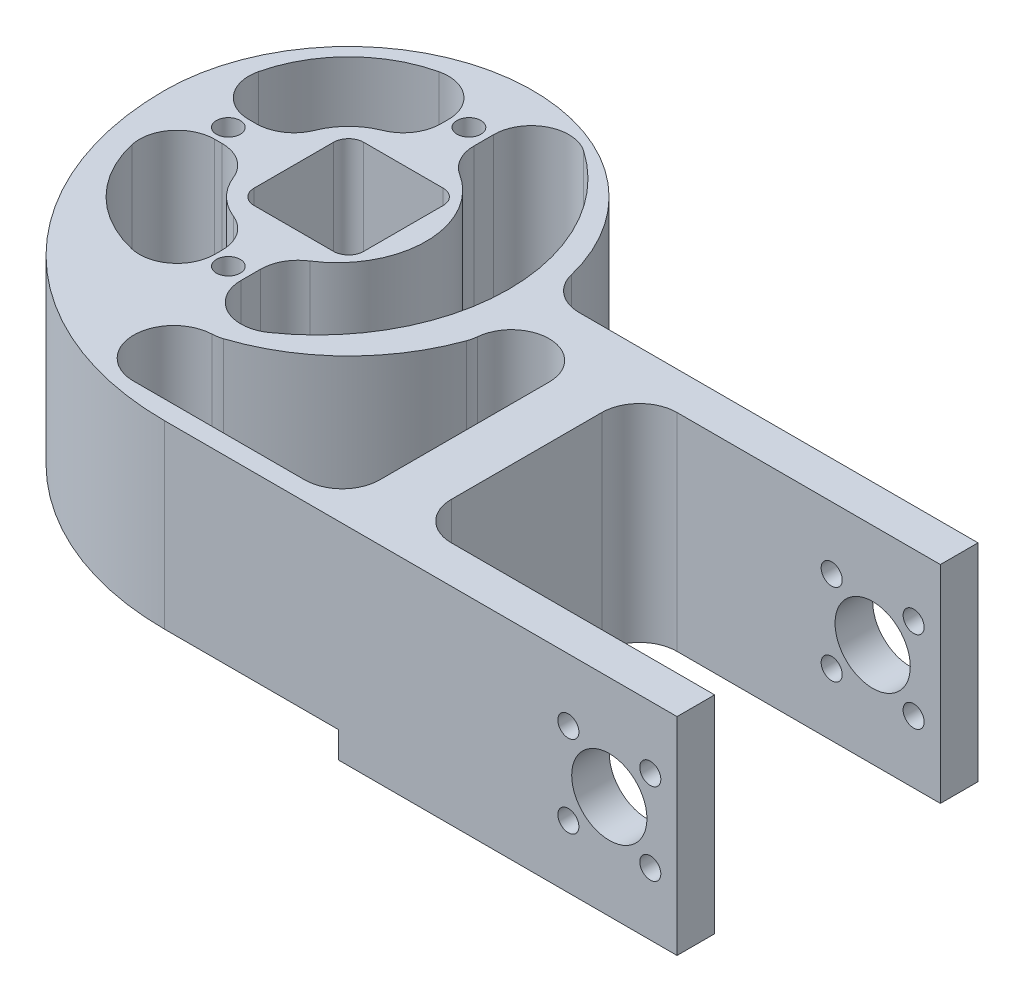
SolidWorks part; units mm, degrees
material "6061-T6 (SS)"
ref_plane "Front Plane" through (0, 0, 0) normal (0, 0, 1) x (1, 0, 0)
ref_plane "Top Plane" through (0, 0, 0) normal (0, 1, 0) x (1, 0, 0)
ref_plane "Right Plane" through (0, 0, 0) normal (1, 0, 0) x (0, 0, -1)
sketch "Sketch1" plane through (0, 0, 0) normal (0, 1, 0) x (1, 0, 0)
  circle A0 centre (0, 0) radius 31.0896
  dimension "D1" = 62.1792
extrude "Boss-Extrude1" add sketch "Sketch1" along normal blind 34.925
sketch "Sketch2" plane through (0, 34.925, 0) normal (0, 1, 0) x (1, 0, 0)
  line L0 (0, 0) -> (-31.0896, 0) construction
  line L1 (0, 0) -> (30.9857, 2.54) construction
  line L2 (46.5427, -48.26) -> (17.1704, -48.26)
  line L4 (46.5427, -48.26) -> (46.5427, 2.54)
  line L7 (30.9857, 2.54) -> (46.5427, 2.54)
  circle A0 centre (0, 0) radius 31.0896 construction
  arc A1 (17.1704, -48.26) -> (-31.0896, 0) centre (17.1704, 0) cw
  circle A2 centre (0, 0) radius 31.0896
  arc A3 (-31.0896, 0) -> (30.9857, 2.54) centre (0, 0) ccw
  dimension "D3" = 2.54
  dimension "D1" = 50.8
  dimension "D2" = 15.557
  dimension "D4" = 0
extrude "Boss-Extrude2" add sketch "Sketch2" against normal blind 30.48
sketch "Sketch3" plane through (0, 34.925, 0) normal (0, 1, 0) x (1, 0, 0)
  line L0 (46.5427, -0.3336) -> (46.5427, -48.26)
  line L1 (17.1704, -48.26) -> (46.5427, -48.26) construction
  line L2 (46.5427, -48.26) -> (103.6927, -48.26)
  line L3 (103.6927, -48.26) -> (103.6927, -41.91)
  line L4 (103.6927, -41.91) -> (52.8927, -41.91)
  line L5 (52.8927, -41.91) -> (52.8927, -3.81)
  line L6 (52.8927, -3.81) -> (103.6927, -3.81)
  line L7 (103.6927, -3.81) -> (103.6927, 2.54)
  line L8 (103.6927, 2.54) -> (46.5427, 2.54)
  line L9 (46.5427, -0.3336) -> (46.5427, 2.54)
  line L10 (46.5427, -48.26) -> (46.5427, 2.54) construction
  dimension "D1" = 57.15
  dimension "D2" = 38.1
  dimension "D3" = 6.35
  dimension "D4" = 6.35
extrude "Boss-Extrude3" add sketch "Sketch3" against normal up to surface (34.925 mm away) up to face at (0, 0, 31.0896)
sketch "Sketch4" plane through (0, 0, -2.54) normal (0, 0, -1) x (-1, 0, 0)
  line L0 (-103.6927, 17.4625) -> (-92.2627, 17.4625) construction
  line L1 (-103.6927, 0) -> (-103.6927, 34.925) construction
  line L2 (-92.2627, 17.4625) -> (-99.1775, 10.5477) construction
  line L3 (-92.2627, 17.4625) -> (-99.1775, 24.3773) construction
  line L4 (-92.2627, 17.4625) -> (-99.1775, 10.5477) construction
  line L5 (-92.2627, 17.4625) -> (-85.3479, 10.5477) construction
  line L6 (-92.2627, 17.4625) -> (-85.3479, 24.3773) construction
  line L8 (-99.1775, 24.3773) -> (-103.6927, 24.3773) construction
  line L9 (-103.6927, 0) -> (-103.6927, 34.925) construction
  line L10 (-99.1775, 10.5477) -> (-103.6927, 10.5477) construction
  circle A0 centre (-92.2627, 17.4625) radius 6.35
  circle A1 centre (-85.3479, 10.5477) radius 1.778
  circle A3 centre (-99.1775, 24.3773) radius 1.778
  circle A4 centre (-99.1775, 10.5477) radius 1.778
  circle A5 centre (-85.3479, 24.3773) radius 1.778
  dimension "D1" = 11.43
  dimension "D2" = 12.7
  dimension "D3" = 3.556
  dimension "D5" = 19.558
  dimension "D4" = 19.558
extrude "Cut-Extrude1" cut sketch "Sketch4" against normal up to surface (50.8 mm away) up to face at (53.3542, 12.7529, 48.26)
sketch "Sketch5" plane through (0, 34.925, 0) normal (0, 1, 0) x (1, 0, 0)
  line L1 (-9.2497, 9.2497) -> (9.2497, 9.2497)
  line L2 (-9.2497, 9.2497) -> (-9.2497, -9.2497)
  line L3 (-9.2497, -9.2497) -> (9.2497, -9.2497)
  line L4 (9.2497, 9.2497) -> (9.2497, -9.2497)
  line L5 (-9.2497, 9.2497) -> (9.2497, -9.2497) construction
  line L6 (-9.2497, -9.2497) -> (9.2497, 9.2497) construction
  point P0 (0, 0)
  dimension "D1" = 26.162
extrude "Cut-Extrude2" cut sketch "Sketch5" against normal up to surface (34.925 mm away) up to face at (0, 0, 31.0896)
fillet "Fillet3" radius 2.54 1 edges at (-9.2497, 17.4625, 9.2497)
fillet "Fillet4" radius 2.54 1 edges at (-9.2497, 17.4625, -9.2497)
fillet "Fillet5" radius 2.54 1 edges at (9.2497, 17.4625, -9.2497)
fillet "Fillet6" radius 2.54 1 edges at (9.2497, 17.4625, 9.2497)
fillet "Fillet8" radius 6.35 1 edges at (30.9857, 19.685, -2.54)
fillet "Fillet9" radius 6.35 1 edges at (52.8927, 17.4625, 41.91)
fillet "Fillet10" radius 6.35 1 edges at (52.8927, 17.4625, 3.81)
sketch "Sketch6" plane through (0, 34.925, 0) normal (0, 1, 0) x (1, 0, 0)
  line L7 (103.6927, 2.54) -> (36.3688, 2.54)
  line L8 (17.1704, -48.26) -> (103.6927, -48.26)
  line L9 (103.6927, -48.26) -> (103.6927, -41.91)
  line L10 (103.6927, -41.91) -> (59.2427, -41.91)
  line L11 (52.8927, -35.56) -> (52.8927, -10.16)
  line L12 (59.2427, -3.81) -> (103.6927, -3.81)
  line L13 (103.6927, -3.81) -> (103.6927, 2.54)
  line L14 (103.6927, 2.54) -> (36.3688, 2.54)
  line L15 (17.1704, -48.26) -> (103.6927, -48.26)
  line L16 (103.6927, -48.26) -> (103.6927, -41.91)
  line L17 (103.6927, -41.91) -> (59.2427, -41.91)
  line L18 (52.8927, -35.56) -> (52.8927, -10.16)
  line L19 (59.2427, -3.81) -> (103.6927, -3.81)
  line L20 (103.6927, -3.81) -> (103.6927, 2.54)
  line L35 (59.2427, -0.635) -> (36.3688, -0.635)
  line L36 (17.1704, -45.085) -> (59.2427, -45.085)
  line L37 (49.7177, -35.56) -> (49.7177, -10.16)
  line L38 (43.6884, -0.635) -> (36.3688, -0.635)
  line L39 (17.1704, -45.085) -> (43.6884, -45.085)
  line L40 (49.7177, -35.56) -> (49.7177, -10.16)
  arc A5 (30.2004, 7.3822) -> (36.3688, 2.54) centre (36.3688, 8.89) ccw
  arc A6 (30.2004, 7.3822) -> (-31.0896, 0) centre (0, 0) ccw
  arc A7 (-31.0896, 0) -> (17.1704, -48.26) centre (17.1704, 0) ccw
  arc A8 (52.8927, -35.56) -> (59.2427, -41.91) centre (59.2427, -35.56) ccw
  arc A9 (59.2427, -3.81) -> (52.8927, -10.16) centre (59.2427, -10.16) ccw
  arc A10 (30.2004, 7.3822) -> (36.3688, 2.54) centre (36.3688, 8.89) ccw
  arc A11 (30.2004, 7.3822) -> (-31.0896, 0) centre (0, 0) ccw
  arc A12 (-31.0896, 0) -> (17.1704, -48.26) centre (17.1704, 0) ccw
  arc A13 (52.8927, -35.56) -> (59.2427, -41.91) centre (59.2427, -35.56) ccw
  arc A14 (59.2427, -3.81) -> (52.8927, -10.16) centre (59.2427, -10.16) ccw
  arc A20 (43.6884, -0.635) -> (49.9101, -8.255) centre (43.6884, -6.985) cw
  arc A21 (43.6884, -45.085) -> (49.9101, -37.465) centre (43.6884, -38.735) ccw
  arc A25 (27.1162, 6.6283) -> (36.3688, -0.635) centre (36.3688, 8.89) ccw
  arc A26 (27.1162, 6.6283) -> (-27.9146, 0) centre (0, 0) ccw
  arc A27 (-27.9146, 0) -> (17.1704, -45.085) centre (17.1704, 0) ccw
  arc A28 (49.7177, -35.56) -> (59.2427, -45.085) centre (59.2427, -35.56) ccw
  arc A29 (59.2427, -0.635) -> (49.7177, -10.16) centre (59.2427, -10.16) ccw
  arc A30 (27.1162, 6.6283) -> (36.3688, -0.635) centre (36.3688, 8.89) ccw
  arc A31 (27.1162, 6.6283) -> (-27.9146, 0) centre (0, 0) ccw
  arc A32 (-27.9146, 0) -> (17.1704, -45.085) centre (17.1704, 0) ccw
  arc A33 (49.7177, -35.56) -> (49.9101, -37.465) centre (59.2427, -35.56) ccw
  arc A34 (49.9101, -8.255) -> (49.7177, -10.16) centre (59.2427, -10.16) ccw
  line M21 (9.2497, 6.7097) -> (9.2497, -6.7097)
  arc M22 (9.2497, -6.7097) -> (6.7097, -9.2497) centre (6.7097, -6.7097) cw
  line M23 (6.7097, -9.2497) -> (-6.7097, -9.2497)
  arc M24 (-6.7097, -9.2497) -> (-9.2497, -6.7097) centre (-6.7097, -6.7097) cw
  line M25 (-9.2497, -6.7097) -> (-9.2497, 6.7097)
  arc M26 (-9.2497, 6.7097) -> (-6.7097, 9.2497) centre (-6.7097, 6.7097) cw
  line M27 (-6.7097, 9.2497) -> (6.7097, 9.2497)
  arc M28 (6.7097, 9.2497) -> (9.2497, 6.7097) centre (6.7097, 6.7097) cw
  dimension "D3" = 6.35
  dimension "D1" = 0
  dimension "D2" = 3.175
extrude "Cut-Extrude3" [suppressed] cut sketch "Sketch6" against normal blind 19.05 contours A34 A20 L38 A30 A31 A32 L39 A21 A33 L40 M28 M21 M22 M23 M24 M25 M26 M27
sketch "Sketch8" [suppressed] plane through (0, 15.875, 0) normal (0, 1, 0) x (1, 0, 0)
  line L1 (35.1127, -2.54) -> (41.4627, -2.54)
  line L2 (28.7627, -8.89) -> (28.7627, -36.83)
  line L3 (47.8127, -8.89) -> (47.8127, -36.83)
  line L6 (35.1127, -43.18) -> (41.4627, -43.18)
  line L7 (103.6927, 2.54) -> (36.3688, 2.54) construction
  line L8 (52.8927, -35.56) -> (52.8927, -10.16) construction
  line L9 (17.1704, -48.26) -> (103.6927, -48.26) construction
  arc A0 (28.7627, -36.83) -> (35.1127, -43.18) centre (35.1127, -36.83) ccw
  arc A1 (47.8127, -36.83) -> (41.4627, -43.18) centre (41.4627, -36.83) cw
  arc A2 (41.4627, -2.54) -> (47.8127, -8.89) centre (41.4627, -8.89) cw
  arc A3 (28.7627, -8.89) -> (35.1127, -2.54) centre (35.1127, -8.89) cw
  dimension "D1" = 6.35
  dimension "D2" = 5.08
  dimension "D3" = 5.08
  dimension "D4" = 19.05
  dimension "D5" = 5.08
extrude "Cut-Extrude4" [suppressed] cut sketch "Sketch8" against normal up to surface (11.43 mm away) up to face at (21.5778, 4.445, 25.8461)
sketch "Sketch9" [suppressed] plane through (0, 15.875, 0) normal (0, 1, 0) x (1, 0, 0)
  line L0 (-9.3373, 19.4097) -> (-9.3373, 18.7747)
  line L1 (-2.9873, 12.4247) -> (3.3627, 12.4247)
  line L2 (9.7127, 18.7747) -> (9.7127, 19.4097)
  line L3 (-2.9873, 25.7597) -> (3.3627, 25.7597)
  line L4 (-6.7097, 9.2497) -> (6.7097, 9.2497) construction
  line L5 (28.7627, -11.8013) -> (28.7627, -8.89) construction
  line L6 (-9.2497, -6.7097) -> (-9.2497, 6.7097) construction
  line L7 (9.2497, 6.7097) -> (9.2497, -6.7097) construction
  line L9 (-9.2497, 0) -> (9.2497, 0) construction
  line L10 (9.7127, -18.7747) -> (9.7127, -19.4097)
  line L11 (-2.9873, -12.4247) -> (3.3627, -12.4247)
  line L12 (-9.3373, -19.4097) -> (-9.3373, -18.7747)
  line L13 (-2.9873, -25.7597) -> (3.3627, -25.7597)
  arc A0 (3.3627, 12.4247) -> (9.7127, 18.7747) centre (3.3627, 18.7747) ccw
  arc A1 (-9.3373, 18.7747) -> (-2.9873, 12.4247) centre (-2.9873, 18.7747) ccw
  arc A2 (-9.3373, 19.4097) -> (-2.9873, 25.7597) centre (-2.9873, 19.4097) cw
  arc A3 (9.7127, 19.4097) -> (3.3627, 25.7597) centre (3.3627, 19.4097) ccw
  arc A4 (3.3627, -12.4247) -> (9.7127, -18.7747) centre (3.3627, -18.7747) cw
  arc A5 (-9.3373, -18.7747) -> (-2.9873, -12.4247) centre (-2.9873, -18.7747) cw
  arc A6 (-9.3373, -19.4097) -> (-2.9873, -25.7597) centre (-2.9873, -19.4097) ccw
  arc A7 (9.7127, -19.4097) -> (3.3627, -25.7597) centre (3.3627, -19.4097) cw
  dimension "D1" = 6.35
  dimension "D2" = 3.175
  dimension "D3" = 16.51
  dimension "D4" = 19.05
  dimension "D5" = 19.05
extrude "Cut-Extrude5" [suppressed] cut sketch "Sketch9" against normal up to surface (11.43 mm away) up to face at (21.5778, 4.445, 25.8461)
sketch "Sketch11" plane through (0, 4.445, 0) normal (0, -1, 0) x (-1, 0, 0)
  line L0 (-44.0027, -10.16) -> (-44.0027, -38.735)
  line L1 (-8.4427, -45.085) -> (-37.6527, -45.085)
  line L2 (-8.4427, -45.085) -> (-8.8214, -38.3416) construction
  line L3 (-8.8214, -38.3416) -> (-9.2001, -31.5981) construction
  line L5 (-17.1704, -48.26) -> (-46.5427, -48.26) construction
  line L6 (-46.5427, -48.26) -> (-46.5427, 2.54) construction
  line L7 (-31.3027, -10.16) -> (-44.0027, -10.16) construction
  arc A0 (-44.0027, -10.16) -> (-31.3322, -9.5481) centre (-37.6527, -10.16) cw
  arc A1 (-44.0027, -38.735) -> (-37.6527, -45.085) centre (-37.6527, -38.735) ccw
  arc A2 (-8.5205, -31.5942) -> (-8.4427, -45.085) centre (-8.8214, -38.3416) cw
  arc A3 (-10.207, -31.2874) -> (-8.5205, -31.5942) centre (-8.2376, -25.2505) ccw
  arc A4 (-30.9916, -11.0728) -> (-10.207, -31.2874) centre (0, 0) ccw
  arc A5 (-31.3322, -9.5481) -> (-30.9916, -11.0728) centre (-25.0118, -8.9363) ccw
  dimension "D1" = 12.7
  dimension "D3" = 3.175
  dimension "D2" = 6.35
  dimension "D5" = 6.7541
  dimension "D7" = 6.35
  dimension "D8" = 6.35
  dimension "D4" = 28.575
  dimension "D6" = 29.21
  dimension "D10" = 2.54
  dimension "D11" = 38.1
extrude "Cut-Extrude6" cut sketch "Sketch11" against normal up to surface (30.48 mm away) up to face at (0, 34.925, 0)
sketch "Sketch12" plane through (0, 0, 0) normal (0, -1, 0) x (1, 0, 0)
  line L0 (0, 0) -> (0, -20.3032) construction
  line L1 (0, 0) -> (0, 20.3032) construction
  line L2 (0, 0) -> (-20.3032, 0) construction
  line L3 (0, 0) -> (20.3032, 0) construction
  circle A0 centre (0, 20.3032) radius 2.0193
  circle A1 centre (-20.3032, 0) radius 2.0193
  circle A2 centre (0, -20.3032) radius 2.0193
  dimension "D1" = 4.0386
extrude "Cut-Extrude7" cut sketch "Sketch12" against normal up to surface (34.925 mm away) up to face at (26.5935, 34.925, 27.5361)
sketch "Sketch13" plane through (0, 0, 0) normal (0, -1, 0) x (1, 0, 0)
  line L0 (3.1444, -18.0174) -> (3.1444, -21.3375)
  line L1 (3.1444, 21.3375) -> (3.1444, 18.0174)
  line L2 (9.2497, 0) -> (13.0597, 0) construction
  line L3 (9.2497, -6.7097) -> (9.2497, 6.7097) construction
  line L4 (13.0597, 0) -> (27.0297, 0) construction
  line L5 (0, 20.3032) -> (3.1444, 20.3032) construction
  line L6 (0, -20.3032) -> (3.1444, -20.3032) construction
  line L7 (-2.8847, -18.4556) -> (-2.8847, -19.7256)
  line L8 (-19.7256, -2.8847) -> (-18.4556, -2.8847)
  line L9 (0, 0) -> (-10.3044, -10.3044) construction
  line L10 (0, 0) -> (-20.475, -20.475) construction
  line L11 (-18.4556, -2.8847) -> (-9.2497, -2.8847) construction
  line L12 (-9.2497, 6.7097) -> (-9.2497, -6.7097) construction
  line L13 (-2.8847, -18.4556) -> (-2.8847, -9.2497) construction
  line L14 (-6.7097, -9.2497) -> (6.7097, -9.2497) construction
  line L15 (-19.0906, -2.8847) -> (-19.0906, -1.6147) construction
  line L16 (-2.8847, -19.0906) -> (-1.6147, -19.0906) construction
  line L17 (0, 0) -> (-31.0896, 0) construction
  line L18 (-2.8847, 18.4556) -> (-2.8847, 19.7256)
  line L19 (-19.7256, 2.8847) -> (-18.4556, 2.8847)
  line L20 (8.5057, -8.5057) -> (9.6865, -9.4692) construction
  line L21 (8.5057, 8.5057) -> (9.6865, 9.4692) construction
  arc A0 (13.1068, 26.5598) -> (13.1068, -26.5598) centre (-5.2651, 0) cw
  arc A1 (6.0965, -12.653) -> (6.0965, 12.653) centre (-1.918, 0) ccw
  arc A2 (3.1444, 21.3375) -> (13.1068, 26.5598) centre (9.4944, 21.3375) cw
  arc A3 (3.1444, 18.0174) -> (6.0965, 12.653) centre (9.4944, 18.0174) ccw
  arc A4 (13.1068, -26.5598) -> (3.1444, -21.3375) centre (9.4944, -21.3375) cw
  arc A5 (3.1444, -18.0174) -> (6.0965, -12.653) centre (9.4944, -18.0174) cw
  arc A6 (-12.5569, -6.8838) -> (-6.8838, -12.5569) centre (-3.1244, -3.1244) ccw
  arc A7 (-10.662, -25.9132) -> (-25.9132, -10.662) centre (-6.0894, -6.0894) cw
  arc A8 (-18.4556, -2.8847) -> (-12.5569, -6.8838) centre (-18.4556, -9.2347) cw
  arc A9 (-2.8847, -19.7256) -> (-10.662, -25.9132) centre (-9.2347, -19.7256) cw
  arc A10 (-2.8847, -18.4556) -> (-6.8838, -12.5569) centre (-9.2347, -18.4556) ccw
  arc A11 (-19.7256, -2.8847) -> (-25.9132, -10.662) centre (-19.7256, -9.2347) ccw
  circle A12 centre (-20.3032, 0) radius 2.0193 construction
  circle A13 centre (0, -20.3032) radius 2.0193 construction
  arc A14 (-10.662, 25.9132) -> (-25.9132, 10.662) centre (-6.0894, 6.0894) ccw
  arc A15 (-2.8847, 19.7256) -> (-10.662, 25.9132) centre (-9.2347, 19.7256) ccw
  arc A16 (-2.8847, 18.4556) -> (-6.8838, 12.5569) centre (-9.2347, 18.4556) cw
  arc A17 (-12.5569, 6.8838) -> (-6.8838, 12.5569) centre (-3.1244, 3.1244) cw
  arc A18 (-18.4556, 2.8847) -> (-12.5569, 6.8838) centre (-18.4556, 9.2347) ccw
  arc A19 (-19.7256, 2.8847) -> (-25.9132, 10.662) centre (-19.7256, 9.2347) cw
  arc A20 (6.7097, -9.2497) -> (9.2497, -6.7097) centre (6.7097, -6.7097) ccw construction
  arc A21 (9.2497, 6.7097) -> (6.7097, 9.2497) centre (6.7097, 6.7097) ccw construction
  dimension "D1" = 6.35
  dimension "D2" = 6.35
  dimension "D3" = 6.35
  dimension "D8" = 1.524
  dimension "D9" = 6.35
  dimension "D10" = 6.35
  dimension "D4" = 3.3201
  dimension "D5" = 3.81
  dimension "D6" = 13.97
  dimension "D7" = 3.1444
  dimension "D11" = 1.27
  dimension "D12" = 9.206
  dimension "D14" = 28.956
  dimension "D15" = 14.5726
  dimension "D16" = 1.27
extrude "Cut-Extrude8" cut sketch "Sketch13" against normal up to surface (34.925 mm away) up to face at (0, 34.925, -18.2839)
